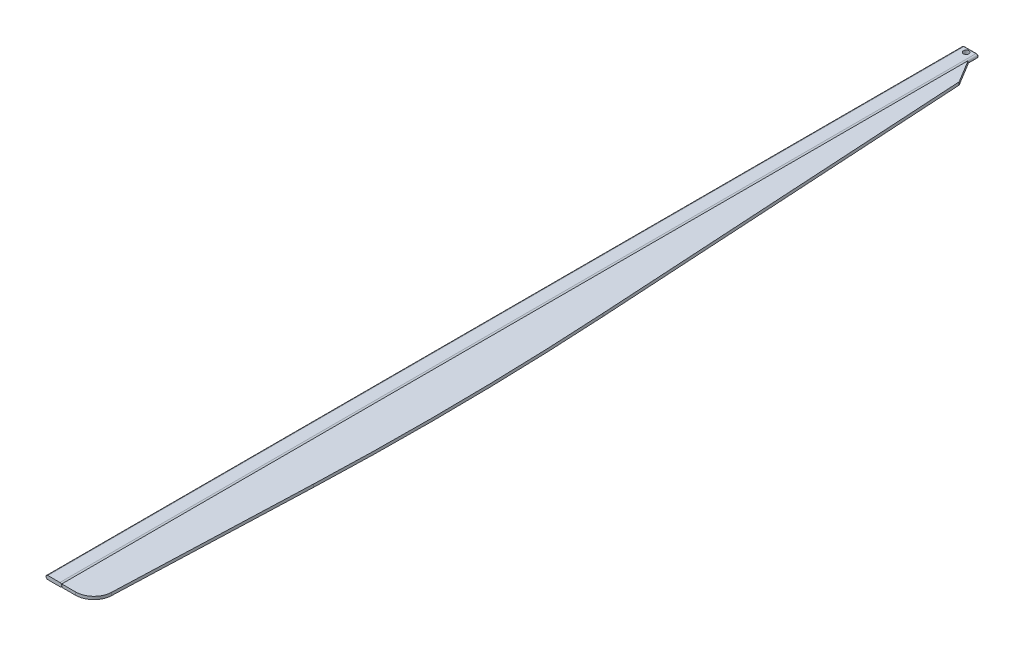
SolidWorks part; units mm, degrees
ref_plane "Front Plane" through (0, 0, 0) normal (0, 0, 1) x (1, 0, 0)
ref_plane "Top Plane" through (0, 0, 0) normal (0, 1, 0) x (1, 0, 0)
ref_plane "Right Plane" through (0, 0, 0) normal (1, 0, 0) x (0, 0, -1)
sketch "Sketch1" plane through (0, 0, 0) normal (0, 0, 1) x (1, 0, 0)
  line L0 (-165, 0) -> (165, 0) construction
  line L1 (-165, 50) -> (165, 50)
  line L2 (-165, -50) -> (165, -50)
  arc A0 (-165, 50) -> (-165, -50) centre (-165, 0) ccw
  arc A1 (165, -50) -> (165, 50) centre (165, 0) ccw
  point P3 (0, 0)
  point P8 (-215, 0)
  point P9 (215, 0)
  dimension "D2" = 100
  dimension "D1" = 430
sketch "Sketch2" plane through (0, 0, 0) normal (0, 1, 0) x (1, 0, 0)
  line L0 (0, 0) -> (0, -25000)
  dimension "D1" = 25000
sweep "Sweep1" add profiles "Sketch1" path "Sketch2"
sketch "Sketch3" plane through (0, 0, 0) normal (0, 1, 0) x (1, 0, 0)
  line L0 (215, -281.2091) -> (591.0525, -901.5244)
  line L1 (591.0525, -901.5244) -> (1200.8515, -11226.0791)
  line L2 (1288.0886, -19204.7473) -> (1090.7079, -24518.5596)
  line L3 (591.0525, -25000) -> (215, -25000)
  line L5 (215, -281.2091) -> (215, -25000)
  line L9 (215, -25000) -> (215, 0) construction
  arc A0 (1200.8515, -11226.0791) -> (1288.0886, -19204.7473) centre (-81697.0591, -16122.2777) cw
  arc A1 (1090.7079, -24518.5596) -> (591.0525, -25000) centre (591.0525, -24500) cw
  point P3 (215, 0)
  point P8 (0, 0)
  point P9 (215, -116.0941)
  point P10 (215, -1435.5071)
  point P15 (215, -934.2475)
  point P16 (359.4506, -288.1471)
  point P17 (1803.6756, -17581.1221)
  point P18 (700.9331, -1846.5373)
  point P19 (215, -175.1061)
  point P22 (416.7924, -1915.176)
  point P23 (215, -1435.5071)
  point P24 (215, -1435.5071)
  point P25 (215, -322.0072)
  point P26 (240.9983, -656.7035)
  point P27 (265.267, -623.3906)
  point P28 (1039.8678, -24907.6321)
  point P29 (0, 0)
  point P30 (0, 0)
  point P31 (0, 0)
  point P32 (770.183, -25000)
  point P33 (919.9513, -25000)
  point P34 (1202.9438, -25000)
  point P35 (1101.4235, -25000)
  point P36 (1189.0664, -25000)
  point P37 (1036.9512, -25000)
  point P38 (297.3375, -516.2353)
  point P39 (215, -341.9041)
  point P40 (215, -281.2091)
  point P41 (298.9895, -405.6853)
  point P42 (1508.3622, -17552.3098)
  point P43 (1682.4628, -16912.8803)
  point P44 (885.9337, -25000)
  point P45 (591.0525, -25000)
  point P46 (1541.1366, -19123.0537)
  point P47 (1275.2096, -19200.7822)
  point P48 (1288.0886, -19204.7473)
  point P49 (591.0525, -901.5244)
  dimension "D2" = 500
sketch "Sketch4" plane through (0, 50, 0) normal (0, 1, 0) x (1, 0, 0)
  line L0 (0, 0) -> (0, -120) construction
  line L1 (165, 0) -> (-165, 0) construction
  circle A0 centre (0, -120) radius 75
  dimension "D1" = 150
  dimension "D2" = 120
extrude "Cut-Extrude1" cut sketch "Sketch4" against normal through all
fillet "Fillet1" radius 20 4 edges at (0, 50, 0) (215, 0, 0) (0, -50, 0) (-215, 0, 0)
extrude "Boss-Extrude1" add sketch "Sketch3" along normal blind 40 and the other way blind 40 separate body
